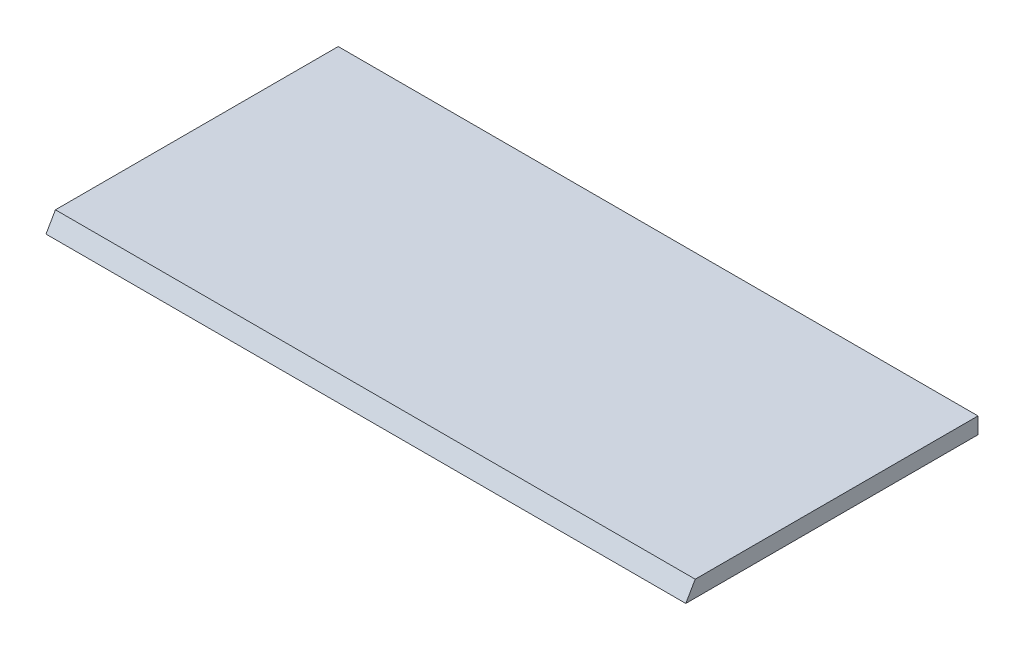
SolidWorks part; units mm, degrees
ref_plane "Alzado" through (0, 0, 0) normal (0, 0, 1) x (1, 0, 0)
ref_plane "Planta" through (0, 0, 0) normal (0, 1, 0) x (1, 0, 0)
ref_plane "Vista lateral" through (0, 0, 0) normal (1, 0, 0) x (0, 0, -1)
sketch "Croquis1" plane through (0, 0, 0) normal (1, 0, 0) x (0, 0, -1)
  line L0 (0, 0) -> (89.52, 0)
  line L1 (89.52, 0) -> (89.52, 5)
  line L2 (89.52, 5) -> (2.8868, 5)
  line L3 (0, 0) -> (2.8868, 5)
  dimension "D1" = 89.52
  dimension "D2" = 5
  dimension "D3" = 120
extrude "Saliente-Extruir1" add sketch "Croquis1" along normal blind 196
shell "Vaciado1" thickness 4 removed face at (98, 0, -44.76)
